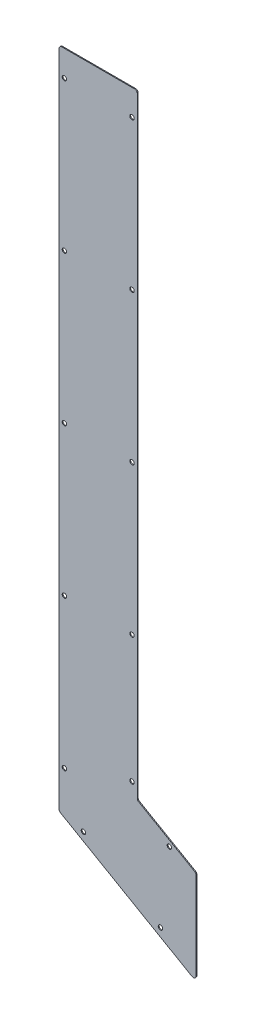
SolidWorks part; units mm, degrees
ref_plane "Front Plane" through (0, 0, 0) normal (0, 0, 1) x (1, 0, 0)
ref_plane "Top Plane" through (0, 0, 0) normal (0, 1, 0) x (1, 0, 0)
ref_plane "Right Plane" through (0, 0, 0) normal (1, 0, 0) x (0, 0, -1)
sketch "Sketch1" plane through (0, 0, 0) normal (0, 0, 1) x (1, 0, 0)
  line L0 (104, 853) -> (16, 853)
  line L1 (16, 853) -> (16, 107.1519)
  line L3 (104, 161.74) -> (104, 853)
  line L4 (104, 161.74) -> (170, 123.6349)
  line L5 (170, 123.6349) -> (170, 18.24)
  line L7 (170, 18.24) -> (16, 107.1519)
  dimension "D1" = 88
  dimension "D2" = 834.76
  dimension "D3" = 60
  dimension "D4" = 143.5
  dimension "D5" = 66
  dimension "D6" = 60
base flange "Base-Flange1" sketch "Sketch1" thickness 1 reverse thickness direction no parameters "D1"=2
sketch "Sketch2" plane through (0, 0, -1) normal (0, 0, -1) x (-1, 0, 0)
  line L0 (-16, 853) -> (-16, 107.1519) construction
  line L1 (-104, 853) -> (-16, 853) construction
  line L2 (-170, 18.24) -> (-170, 123.6349) construction
  line L4 (-130, 50.7349) -> (-43.3975, 100.7349) construction
  line L5 (-16, 107.1519) -> (-170, 18.24) construction
  line L6 (-170, 123.6349) -> (-151.7357, 123.6349) construction
  circle A0 centre (-22, 824) radius 2.5
  circle A1 centre (-98, 824) radius 2.5
  circle A2 centre (-98, 656) radius 2.5
  circle A3 centre (-98, 488) radius 2.5
  circle A4 centre (-98, 320) radius 2.5
  circle A8 centre (-22, 656) radius 2.5
  circle A9 centre (-22, 488) radius 2.5
  circle A10 centre (-22, 320) radius 2.5
  circle A11 centre (-22, 152) radius 2.5
  circle A12 centre (-98, 152) radius 2.5 [skipped]
  circle A13 centre (-98, 177) radius 2.5
  circle A14 centre (-140, 134.5649) radius 2.5
  circle A15 centre (-130, 50.7349) radius 2.5
  circle A16 centre (-43.3975, 100.7349) radius 2.5
  dimension "D1" = 5
  dimension "D2" = 6
  dimension "D3" = 29
  dimension "D6" = 15.26
  dimension "D7" = 30
  dimension "D8" = 10.93
  dimension "D9" = 72.9
  dimension "D11" = 40
  dimension "D10" = 100
  dimension "D4" = 2
  dimension "D5" = 5
extrude "Cut-Extrude1" cut sketch "Sketch2" against normal blind 10 normal cut yes
fillet "Fillet1" radius 3 6 edges at (104, 161.74, -0.5) (170, 123.6349, -0.5) (16, 853, -0.5) (104, 853, -0.5) (16, 107.1519, -0.5) (170, 18.24, -0.5)
sketch "Bend-Lines1" [suppressed] plane through (0, 0, 0) normal (0, 1, 0) x (1, 0, 0)
sketch "Bounding-Box1" [suppressed] plane through (0, 0, 0) normal (0, 1, 0) x (1, 0, 0)
sheet metal parameters "Sheet-Metal1" thickness 1 parameters "D1"=2
flat pattern "Flat-Pattern1" [suppressed]
sketch "Bend-Lines2" plane through (0, 0, 0) normal (0, 1, 0) x (1, 0, 0)
sketch3d "Bounding-Box2" [suppressed]
  line L0 (162, 1047, 0) -> (162, 0, 0) construction
  line L1 (0, 1047, 0) -> (0, 0, 0) construction
  line L2 (162, 1047, 0) -> (0, 1047, 0) construction
  line L3 (162, 0, 0) -> (0, 0, 0) construction
sheet metal parameters "Sheet-Metal2" thickness 1 parameters "D1"=2
flat pattern "Flat-Pattern1"
sketch "Bend-Lines2" plane through (0, 0, 0) normal (0, 1, 0) x (1, 0, 0)
sketch3d "Bounding-Box2" [suppressed]
  line L0 (170, 20.4363, 0) -> (170, 853, 0) construction
  line L1 (16, 20.4363, 0) -> (16, 853, 0) construction
  line L2 (170, 20.4363, 0) -> (16, 20.4363, 0) construction
  line L3 (170, 853, 0) -> (16, 853, 0) construction
